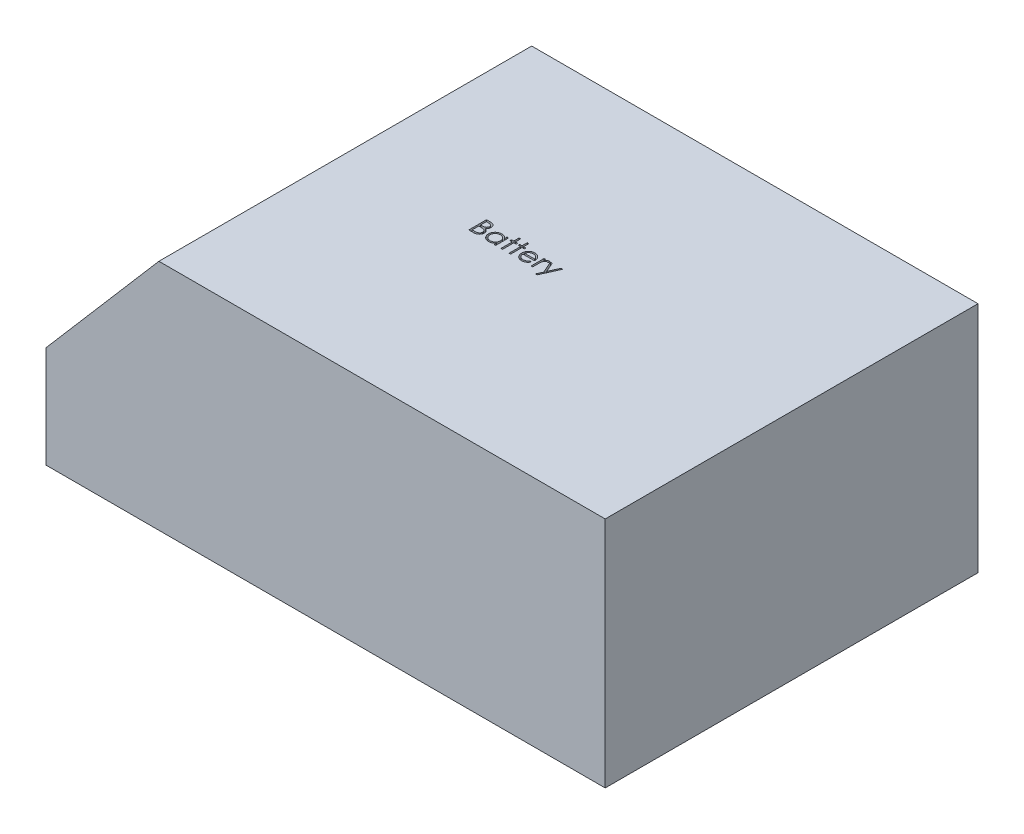
SolidWorks part; units mm, degrees
ref_plane "정면" through (0, 0, 0) normal (0, 0, 1) x (1, 0, 0)
ref_plane "윗면" through (0, 0, 0) normal (0, 1, 0) x (1, 0, 0)
ref_plane "우측면" through (0, 0, 0) normal (1, 0, 0) x (0, 0, -1)
sketch "Sketch1" plane through (0, 0, 0) normal (0, 1, 0) x (1, 0, 0)
  line L1 (300, -200) -> (-300, -200)
  line L2 (300, -200) -> (300, 200)
  line L3 (300, 200) -> (-300, 200)
  line L4 (-300, -200) -> (-300, 200)
  line L5 (300, -200) -> (-300, 200) construction
  line L6 (300, 200) -> (-300, -200) construction
  point P0 (0, 0)
  dimension "D1" = 600
  dimension "D2" = 400
extrude "Boss-Extrude1" add sketch "Sketch1" along normal blind 125 and the other way blind 125
sketch "Sketch2" plane through (0, 125, 0) normal (0, 1, 0) x (1, 0, 0)
  text T0 "Battery" font "Century Gothic" height in points 72
extrude "Cut-Extrude1" cut sketch "Sketch2" against normal blind 30
sketch "Sketch3" plane through (-300, 0, 0) normal (-1, 0, 0) x (0, 0, 1)
  text T0 "Driver Side" font "Century Gothic" height in points 72
extrude "Cut-Extrude2" cut sketch "Sketch3" against normal blind 30
sketch "Sketch4" plane through (0, 0, 200) normal (0, 0, 1) x (1, 0, 0)
  line L0 (-300, 125) -> (-178.8752, 125)
  line L1 (-300, 125) -> (300, 125) construction
  line L2 (-178.8752, 125) -> (-300, -15.9122)
  line L3 (-300, -15.9122) -> (-300, 125)
  line L4 (-300, -125) -> (-300, 125) construction
  point P7 (-192.0439, 125)
  point P8 (-300, 5.3898)
  point P9 (-300, -24.1427)
  point P12 (-183.8134, 125)
  point P13 (-300, -15.9122)
  point P14 (-178.8752, 125)
extrude "Cut-Extrude3" cut sketch "Sketch4" against normal through all
